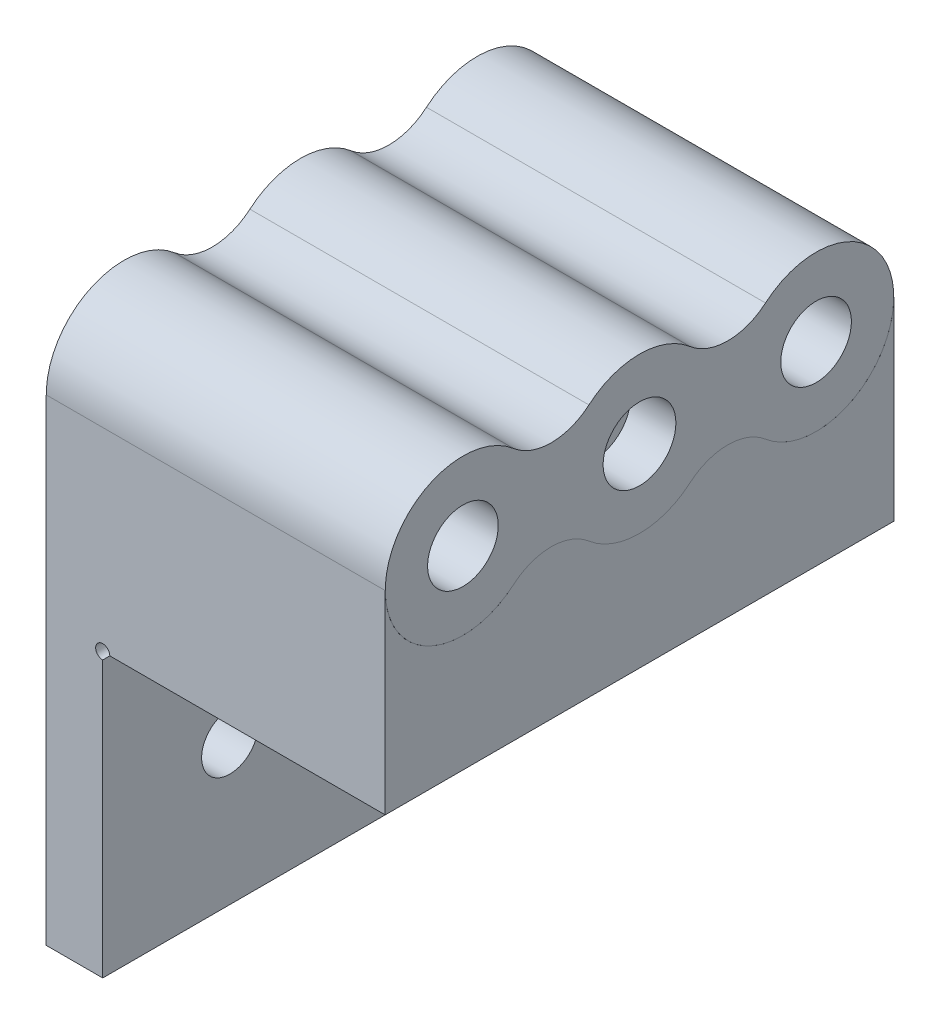
SolidWorks part; units mm, degrees
ref_plane "Front Plane" through (0, 0, 0) normal (0, 0, 1) x (1, 0, 0)
ref_plane "Top Plane" through (0, 0, 0) normal (0, 1, 0) x (1, 0, 0)
ref_plane "Right Plane" through (0, 0, 0) normal (1, 0, 0) x (0, 0, -1)
sketch "Sketch1" plane through (0, 0, 0) normal (0, 0, 1) x (1, 0, 0)
  line L0 (0, 0) -> (4, 0)
  line L1 (55, 0) -> (-55, 0) construction
  line L2 (4, 0) -> (4, 19.5)
  line L3 (4.5, 20) -> (24, 20)
  line L4 (24, 20) -> (24, 24)
  line L5 (24, 24) -> (0, 24)
  line L6 (0, -55) -> (0, 55) construction
  line L7 (0, 24) -> (0, 0)
  line L8 (4, 20) -> (4.5, 20) construction
  line L9 (4, 20) -> (4, 19.5) construction
  arc A0 (4.5, 20) -> (4, 19.5) centre (4, 20) ccw
  point P6 (2, 0)
  dimension "D6" = 0.5
  dimension "D1" = 20
  dimension "D2" = 20
  dimension "D3" = 4
extrude "Boss-Extrude1" add sketch "Sketch1" along normal mid plane 36
sketch "Sketch3" plane through (24, 0, 0) normal (-1, 0, 0) x (0, 0, 1)
  line L0 (12.5, 33.75) -> (-12.5, 33.75) construction
  line L1 (0, -13.2) -> (0, 13.2) construction
  line L2 (18, 20) -> (-18, 20) construction
  arc A0 (8.9193, 29.5753) -> (3.5807, 29.5753) centre (6.25, 26.4632) ccw
  arc A1 (3.5807, 29.5753) -> (-3.5807, 29.5753) centre (0, 33.75) cw
  arc A2 (-3.5807, 29.5753) -> (-8.9193, 29.5753) centre (-6.25, 26.4632) ccw
  arc A3 (-8.9193, 29.5753) -> (-8.9193, 37.9247) centre (-12.5, 33.75) cw
  arc A4 (-8.9193, 37.9247) -> (-3.5807, 37.9247) centre (-6.25, 41.0368) ccw
  arc A5 (-3.5807, 37.9247) -> (3.5807, 37.9247) centre (0, 33.75) cw
  arc A6 (3.5807, 37.9247) -> (8.9193, 37.9247) centre (6.25, 41.0368) ccw
  arc A7 (8.9193, 37.9247) -> (8.9193, 29.5753) centre (12.5, 33.75) cw
  point P19 (0, 33.75)
  dimension "D1" = 5.5
  dimension "D2" = 5.5
  dimension "D5" = 4.1
  dimension "D3" = 25
  dimension "D4" = 13.75
extrude "Boss-Extrude2" add sketch "Sketch3" along normal up to surface (24 mm away) up to face at (0, 12, 0)
sketch "Sketch9" plane through (0, 0, 0) normal (-1, 0, 0) x (0, 0, 1)
  line L0 (-18, 24) -> (-18, 33.75)
  line L1 (-18, 24) -> (18, 24)
  line L2 (18, 24) -> (18, 33.75)
  line L3 (18, 24) -> (-18, 24) construction
  arc A2 (-18, 33.75) -> (-8.9193, 29.5753) centre (-12.5, 33.75) ccw
  arc A3 (-8.9193, 29.5753) -> (-3.5807, 29.5753) centre (-6.25, 26.4632) cw
  arc A4 (-3.5807, 29.5753) -> (3.5807, 29.5753) centre (0, 33.75) ccw
  arc A5 (3.5807, 29.5753) -> (8.9193, 29.5753) centre (6.25, 26.4632) cw
  arc A6 (8.9193, 29.5753) -> (18, 33.75) centre (12.5, 33.75) ccw
  arc A7 (-8.9193, 37.9247) -> (-8.9193, 29.5753) centre (-12.5, 33.75) ccw construction
  arc A8 (8.9193, 29.5753) -> (8.9193, 37.9247) centre (12.5, 33.75) ccw construction
extrude "Boss-Extrude3" add sketch "Sketch9" against normal up to surface (24 mm away) up to face at (24, 22, 0)
sketch "Sketch4" plane through (24, 0, 0) normal (1, 0, 0) x (0, 0, -1)
  circle A0 centre (-12.5, 33.75) radius 2.5
  circle A1 centre (12.5, 33.75) radius 2.5
  circle A2 centre (0, 33.75) radius 2.575
  dimension "D1" = 5
  dimension "D2" = 5
  dimension "D3" = 5.15
extrude "Cut-Extrude1" cut sketch "Sketch4" against normal through all contours A0 | A1 region at (24, 33.75, 12.5) region at (24, 33.75, -12.5)
extrude "Cut-Extrude2" cut sketch "Sketch4<3>" against normal blind 3.2 contours A2 region at (24, 33.75, 0)
sketch "Sketch4<3>" plane through (24, 0, 0) normal (1, 0, 0) x (0, 0, -1) same geometry as "Sketch4"
sketch "Sketch6" plane through (4, 0, 0) normal (1, 0, 0) x (0, 0, -1)
  line L0 (-18, 0) -> (18, 0) construction
  line L1 (-9, 10) -> (9, 10) construction
  line L2 (0, 13.2) -> (0, -13.2) construction
  line L3 (-18, 0) -> (-18, 19.5) construction
  circle A0 centre (-9, 10) radius 2
  circle A1 centre (9, 10) radius 2
  point P7 (0, 10)
  dimension "D3" = 4
  dimension "D1" = 10
  dimension "D2" = 9
extrude "Cut-Extrude3" cut sketch "Sketch6" against normal through all both and the other way through all
ref_plane "Plane1" through (0, 39.25, 0) normal (0, 1, 0) x (1, 0, 0)
sketch "Sketch8" plane through (0, 39.25, 0) normal (0, 1, 0) x (1, 0, 0)
  line L0 (-13.2, 0) -> (13.2, 0) construction
  line L2 (0, 3.5807) -> (0, -3.5807) construction
  circle A0 centre (14, 0) radius 4.25
  circle A1 centre (14, 0) radius 2
  dimension "D1" = 8.5
  dimension "D2" = 4
  dimension "D3" = 14
extrude "Cut-Extrude4" cut sketch "Sketch8" against normal through all contours A1 region at (14, 39.25, 0)
extrude "Cut-Extrude5" cut sketch "Sketch8<3>" against normal offset from surface (16.25 mm away) 3 contours A0 A1 region at (9.8702, 39.25, 0) up to face at (14, 20, 2)
sketch "Sketch8<3>" plane through (0, 39.25, 0) normal (0, 1, 0) x (1, 0, 0) same geometry as "Sketch8"
